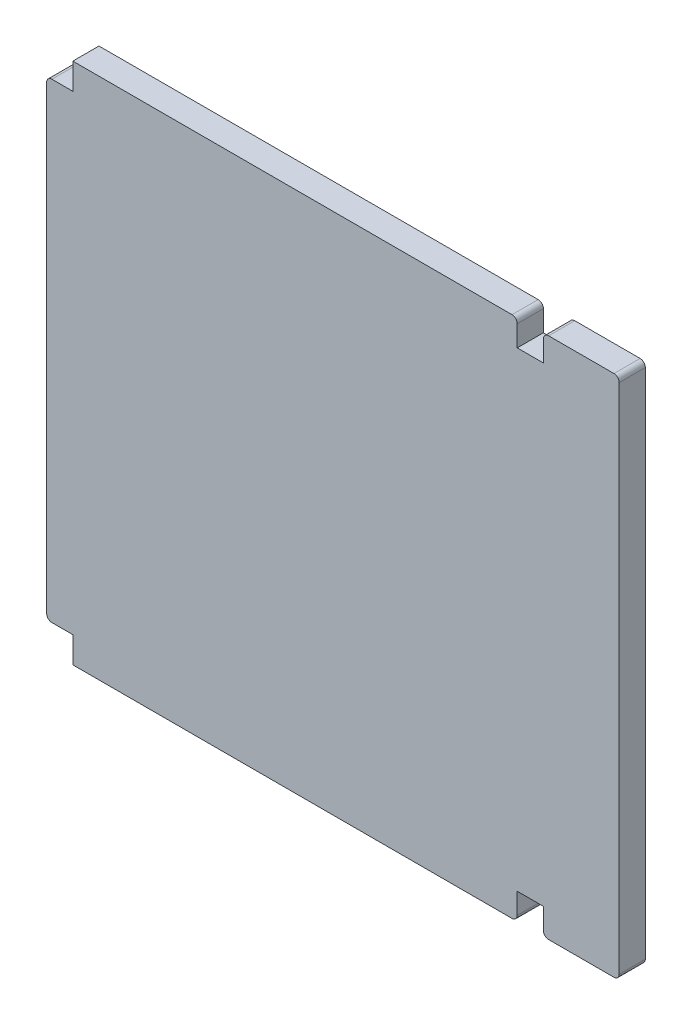
SolidWorks part; units mm, degrees
ref_plane "Front" through (0, 0, 0) normal (0, 0, 1) x (1, 0, 0)
ref_plane "Top" through (0, 0, 0) normal (0, 1, 0) x (1, 0, 0)
ref_plane "Right" through (0, 0, 0) normal (1, 0, 0) x (0, 0, -1)
sketch "Sketch1" plane through (0, 0, 0) normal (0, 0, 1) x (1, 0, 0)
  line L0 (0, 95) -> (0, 100)
  line L1 (0, 0) -> (85, 0)
  line L2 (0, 0) -> (0, 5)
  line L3 (0, 100) -> (85, 100)
  line L4 (85, 0) -> (85, 5)
  line L5 (0, 95) -> (-5, 95)
  line L7 (0, 5) -> (-5, 5)
  line L8 (-5, 95) -> (-5, 5)
  line L9 (85, 95) -> (90, 95)
  line L11 (85, 5) -> (90, 5)
  line L13 (85, 95) -> (85, 100)
  line L14 (90, 100) -> (90, 95)
  line L15 (90, 100) -> (104.5, 100)
  line L16 (90, 0) -> (104.5, 0)
  line L17 (104.5, 100) -> (104.5, 0)
  line L18 (90, 5) -> (90, 0)
  dimension "D1" = 85
  dimension "D2" = 5
  dimension "D3" = 5
  dimension "D4" = 5
  dimension "D5" = 5
  dimension "D6" = 100
  dimension "D7" = 5
  dimension "D10" = 14.5
extrude "Boss-Extrude1" add sketch "Sketch1" along normal blind 5
fillet "Fillet1" radius 1 8 edges at (104.5, 0, 2.5) (104.5, 100, 2.5) (85, 100, 2.5) (90, 100, 2.5) (-5, 95, 2.5) (-5, 5, 2.5) (85, 0, 2.5) (90, 0, 2.5)
